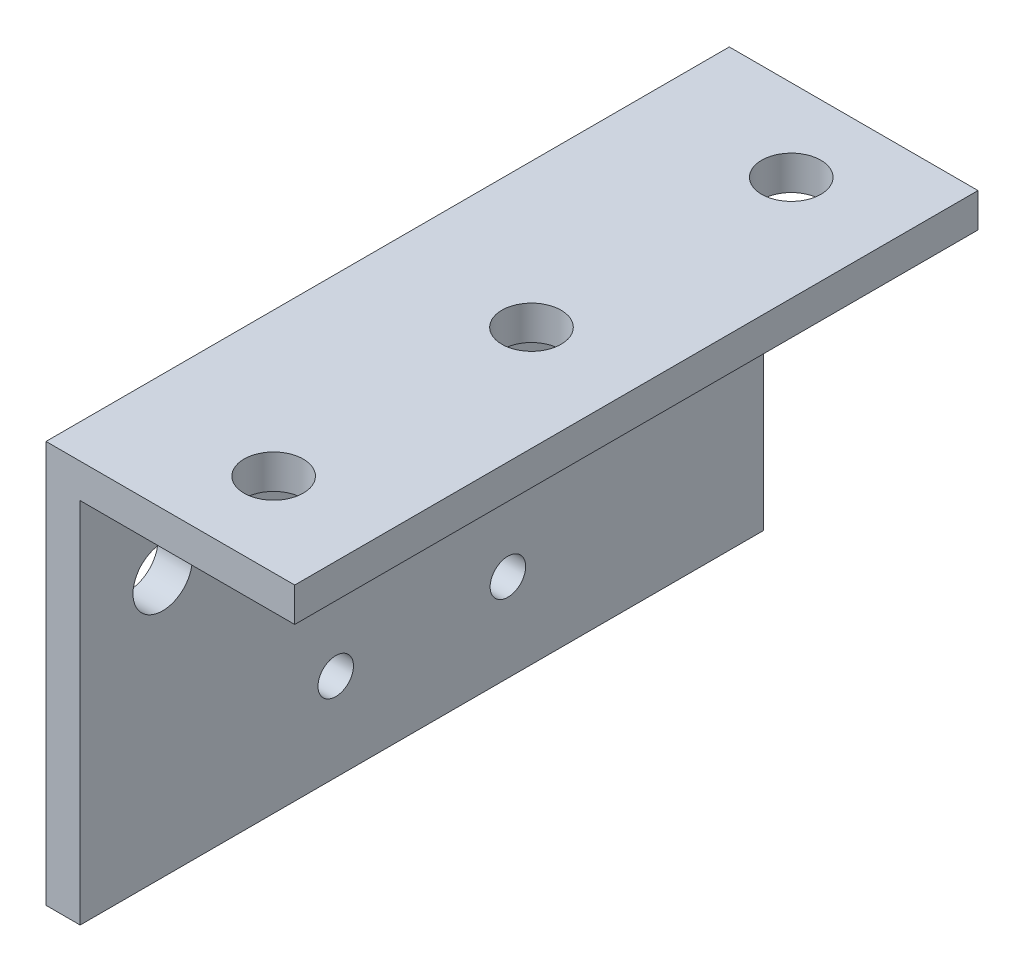
SolidWorks part; units mm, degrees
material "6061 Alloy"
ref_plane "Front Plane" through (0, 0, 0) normal (0, 0, 1) x (1, 0, 0)
ref_plane "Top Plane" through (0, 0, 0) normal (0, 1, 0) x (1, 0, 0)
ref_plane "Right Plane" through (0, 0, 0) normal (1, 0, 0) x (0, 0, -1)
sketch "Sketch1" plane through (0, 0, 0) normal (0, 0, 1) x (1, 0, 0)
  line L0 (0, 0) -> (0, 37.338)
  line L1 (0, 37.338) -> (23.114, 37.338)
  line L2 (23.114, 37.338) -> (23.114, 34.163)
  line L3 (0, 0) -> (3.175, 0)
  line L4 (3.175, 0) -> (3.175, 34.163)
  line L5 (3.175, 34.163) -> (23.114, 34.163)
  dimension "D1" = 37.338
  dimension "D2" = 23.114
  dimension "D3" = 3.175
  dimension "D4" = 3.175
extrude "Boss-Extrude1" add sketch "Sketch1" along normal blind 63.5
sketch "Sketch21" plane through (0, 0, 0) normal (-1, 0, 0) x (0, 0, 1)
  line L0 (31.75, 0) -> (31.75, 37.338) construction
  line L1 (63.5, 0) -> (0, 0) construction
  line L2 (63.5, 37.338) -> (0, 37.338) construction
  point P3 (31.75, 18.669)
sketch "Sketch28" plane through (0, 37.338, 0) normal (0, 1, 0) x (1, 0, 0)
  line L0 (23.114, -31.75) -> (0, -31.75) construction
  line L2 (23.114, -63.5) -> (23.114, 0) construction
  point P3 (11.557, -31.75)
sketch "Sketch29" plane through (0, 0, 0) normal (-1, 0, 0) x (0, 0, 1)
  line L0 (0, 24.2082) -> (63.5, 24.2082) construction
  line L1 (0, 37.338) -> (0, 0) construction
  line L2 (63.5, 37.338) -> (63.5, 0) construction
sketch "Sketch30" plane through (0, 37.338, 0) normal (0, 1, 0) x (1, 0, 0)
  line L0 (13.3686, 0) -> (13.3686, -63.5) construction
  line L1 (23.114, 0) -> (0, 0) construction
  line L2 (23.114, -63.5) -> (0, -63.5) construction
  line L3 (0, -63.5) -> (0, 0) construction
  dimension "D1" = 13.3686
sketch "Sketch31" plane through (0, 0, 0) normal (-1, 0, 0) x (0, 0, 1)
  line L0 (31.75, 24.2082) -> (10.16, 24.2082) construction
  line L1 (0, 24.2082) -> (63.5, 24.2082) construction
  line L2 (31.75, 24.2082) -> (53.34, 24.2082) construction
sketch "Sketch32" plane through (0, 37.338, 0) normal (0, 1, 0) x (1, 0, 0)
  line L0 (13.3686, -31.75) -> (13.3686, -53.34) construction
  line L1 (13.3686, 0) -> (13.3686, -63.5) construction
  line L2 (13.3686, -31.75) -> (13.3686, -10.16) construction
hole_wizard "M5 Clearance Hole1" positions "Sketch35" profile "Sketch36" hole size "M5" standard "ANSI Metric" end condition through all
sketch "Sketch35" plane through (0, 0, 0) normal (-1, 0, 0) x (0, 0, 1)
  line L0 (0, 24.2082) -> (63.5, 24.2082) construction
  point P0 (55.8413, 24.2082)
sketch "Sketch36" plane through (0, 24.2082, 55.8413) normal (0, 1, 0) x (0, 0, 1)
  line L0 (0, 0) -> (0, 23.114)
  line L1 (0, 23.114) -> (2.75, 23.114)
  line L2 (2.75, 23.114) -> (2.75, 0)
  line L5 (2.75, 0) -> (0, 0)
  line L11 (0, -6.35) -> (0, 107.95) construction
  dimension "Thru Hole Dia." = 5.5
  dimension "Thru Hole Depth" = 23.114
hole_wizard "M5 Clearance Hole2" positions "Sketch37" profile "Sketch38" hole size "M5" standard "ANSI Metric" end condition through all
sketch "Sketch37" plane through (0, 0, 0) normal (-1, 0, 0) x (0, 0, 1)
  line L0 (0, 24.2082) -> (63.5, 24.2082) construction
  point P0 (7.6776, 24.2082)
sketch "Sketch38" plane through (0, 24.2082, 7.6776) normal (0, 1, 0) x (0, 0, 1)
  line L0 (0, 0) -> (0, 23.114)
  line L1 (0, 23.114) -> (2.75, 23.114)
  line L2 (2.75, 23.114) -> (2.75, 0)
  line L5 (2.75, 0) -> (0, 0)
  line L11 (0, -6.35) -> (0, 107.95) construction
  dimension "Thru Hole Dia." = 5.5
  dimension "Thru Hole Depth" = 23.114
hole_wizard "M5 Clearance Hole3" positions "Sketch39" profile "Sketch40" hole size "M5" standard "ANSI Metric" end condition through all
sketch "Sketch39" plane through (0, 37.338, 0) normal (0, 1, 0) x (1, 0, 0)
  point P0 (13.3686, -31.75)
sketch "Sketch40" plane through (13.3686, 37.338, 31.75) normal (1, 0, 0) x (0, 0, 1)
  line L0 (0, 0) -> (0, 37.338)
  line L1 (0, 37.338) -> (2.75, 37.338)
  line L2 (2.75, 37.338) -> (2.75, 0)
  line L5 (2.75, 0) -> (0, 0)
  line L11 (0, -6.35) -> (0, 107.95) construction
  dimension "Thru Hole Dia." = 5.5
  dimension "Thru Hole Depth" = 37.338
hole_wizard "M5 Clearance Hole4" positions "Sketch43" profile "Sketch44" hole size "M5" standard "ANSI Metric" end condition through all
sketch "Sketch43" plane through (0, 37.338, 0) normal (0, 1, 0) x (1, 0, 0)
  line L0 (13.3686, 0) -> (13.3686, -63.5) construction
  point P0 (13.3686, -55.7137)
sketch "Sketch44" plane through (13.3686, 37.338, 55.7137) normal (1, 0, 0) x (0, 0, 1)
  line L0 (0, 0) -> (0, 37.338)
  line L1 (0, 37.338) -> (2.75, 37.338)
  line L2 (2.75, 37.338) -> (2.75, 0)
  line L5 (2.75, 0) -> (0, 0)
  line L11 (0, -6.35) -> (0, 107.95) construction
  dimension "Thru Hole Dia." = 5.5
  dimension "Thru Hole Depth" = 37.338
hole_wizard "M5 Clearance Hole5" positions "Sketch49" profile "Sketch50" hole size "M5" standard "ANSI Metric" end condition through all
sketch "Sketch49" plane through (0, 37.338, 0) normal (0, 1, 0) x (1, 0, 0)
  line L0 (13.3686, 0) -> (13.3686, -63.5) construction
  line L1 (23.114, 0) -> (0, 0) construction
  point P0 (13.3686, -7.6106)
  dimension "D1" = 7.6106
sketch "Sketch50" plane through (13.3686, 37.338, 7.6106) normal (1, 0, 0) x (0, 0, 1)
  line L0 (0, 0) -> (0, 37.338)
  line L1 (0, 37.338) -> (2.75, 37.338)
  line L2 (2.75, 37.338) -> (2.75, 0)
  line L5 (2.75, 0) -> (0, 0)
  line L11 (0, -6.35) -> (0, 107.95) construction
  dimension "Thru Hole Dia." = 5.5
  dimension "Thru Hole Depth" = 37.338
sketch "Sketch51" plane through (0, 0, 0) normal (-1, 0, 0) x (0, 0, 1)
  line L0 (63.5, 34.163) -> (0, 34.163) construction
  line L1 (39.75, 24.163) -> (23.75, 24.163) construction
  line L2 (39.75, 24.163) -> (39.75, 8.163) construction
  line L3 (39.75, 8.163) -> (23.75, 8.163) construction
  line L4 (23.75, 24.163) -> (23.75, 8.163) construction
  line L5 (39.75, 24.163) -> (23.75, 8.163) construction
  line L6 (39.75, 8.163) -> (23.75, 24.163) construction
  line L7 (31.75, 37.338) -> (31.75, 0) construction
  line L8 (63.5, 37.338) -> (0, 37.338) construction
  line L9 (63.5, 0) -> (0, 0) construction
  circle A0 centre (31.75, 16.163) radius 5 construction
  point P0 (31.75, 16.163)
  dimension "D4" = 10
  dimension "D1" = 10
  dimension "D2" = 16
  dimension "D3" = 16
hole_wizard "Tap Drill for M4x0.7 Tap2" positions "Sketch52" profile "Sketch53" hole size "M4x0.7" standard "ANSI Metric" end condition through all
sketch "Sketch52" plane through (0, 0, 0) normal (-1, 0, 0) x (0, 0, 1)
  point P0 (23.75, 24.163)
  point P3 (23.75, 8.163)
  point P6 (39.75, 8.163)
  point P9 (39.75, 24.163)
sketch "Sketch53" plane through (0, 24.163, 23.75) normal (0, 1, 0) x (0, 0, 1)
  line L0 (0, 0) -> (0, 23.114)
  line L1 (0, 23.114) -> (1.65, 23.114)
  line L2 (1.65, 23.114) -> (1.65, 0)
  line L5 (1.65, 0) -> (0, 0)
  line L11 (0, -6.35) -> (0, 107.95) construction
  dimension "Thru Hole Dia." = 3.3
  dimension "Thru Hole Depth" = 23.114
sketch "Sketch54" plane through (0, 37.338, 0) normal (0, 1, 0) x (1, 0, 0)
  line L0 (0, -31.75) -> (23.114, -31.75) construction
  line L1 (0, -63.5) -> (0, 0) construction
  line L2 (23.114, -63.5) -> (23.114, 0) construction
